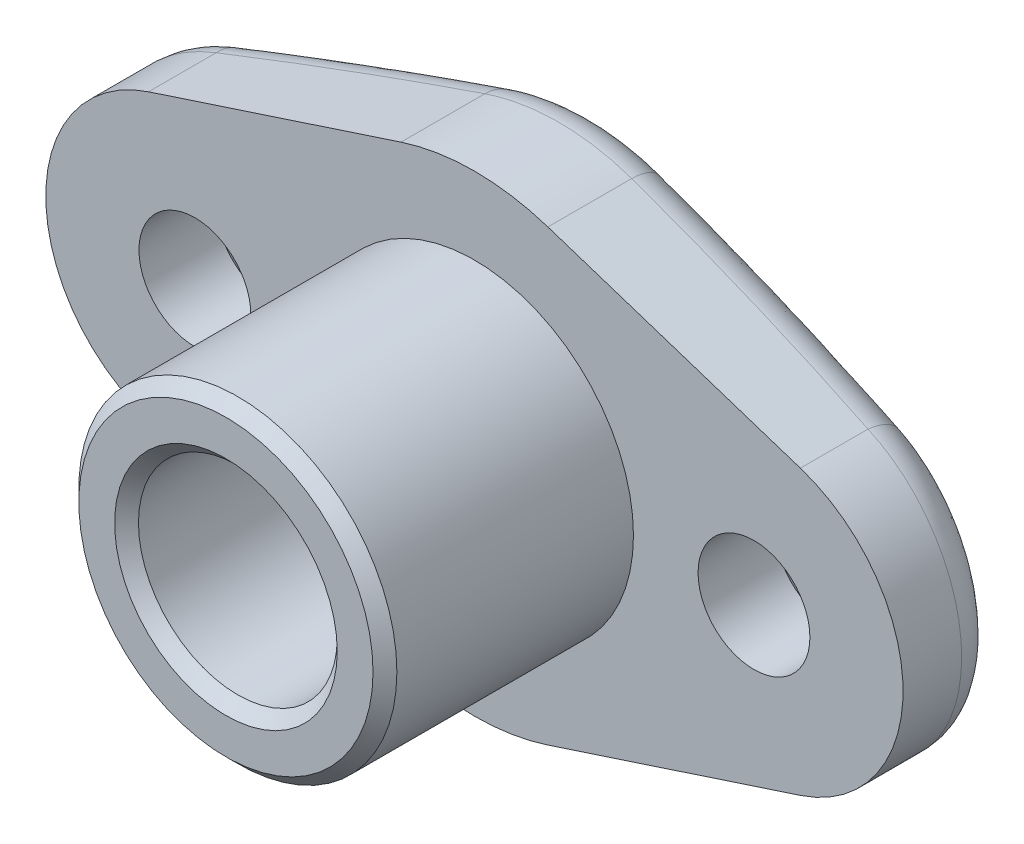
SolidWorks part; units mm, degrees
ref_plane "Front Plane" through (0, 0, 0) normal (0, 0, 1) x (1, 0, 0)
ref_plane "Top Plane" through (0, 0, 0) normal (0, 1, 0) x (1, 0, 0)
ref_plane "Right Plane" through (0, 0, 0) normal (1, 0, 0) x (0, 0, -1)
sketch "Sketch1" plane through (0, 0, 0) normal (0, 0, 1) x (1, 0, 0)
  line L0 (-10.4114, 4.5262) -> (-2.346, 7.1664)
  line L1 (2.346, 7.1664) -> (10.4114, 4.5262)
  line L2 (10.4114, -4.5262) -> (2.346, -7.1664)
  line L3 (-2.346, -7.1664) -> (-10.4114, -4.5262)
  line L4 (-8.9297, 0) -> (8.9297, 0) construction
  line L5 (-13.6922, 0) -> (13.6922, 0) construction
  circle A0 centre (0, 0) radius 7.5406
  circle A1 centre (8.9297, 0) radius 1.7859
  circle A2 centre (-8.9297, 0) radius 1.7859
  arc A3 (-10.4114, 4.5262) -> (-10.4114, -4.5262) centre (-8.9297, 0) ccw
  arc A4 (10.4114, -4.5262) -> (10.4114, 4.5262) centre (8.9297, 0) ccw
  circle A5 centre (0, 0) radius 3.175
  dimension "shaft dia" = 6.35
sketch "Sketch2" plane through (0, 0, 0) normal (0, 1, 0) x (1, 0, 0)
  line L0 (0, 0) -> (0, -11.9062) construction
  point P3 (0, -3.9688)
sketch "Sketch3" plane through (0, 0, 0) normal (0, 0, 1) x (1, 0, 0)
  line L0 (2.346, 7.1664) -> (10.4114, 4.5262) construction
  line L1 (10.4114, -4.5262) -> (2.346, -7.1664) construction
  line L2 (-10.4114, 4.5262) -> (-2.346, 7.1664) construction
  line L3 (-2.346, -7.1664) -> (-10.4114, -4.5262) construction
  line L4 (2.346, 7.1664) -> (10.4114, 4.5262)
  line L5 (10.4114, -4.5262) -> (2.346, -7.1664)
  line L6 (-10.4114, 4.5262) -> (-2.346, 7.1664)
  line L7 (-2.346, -7.1664) -> (-10.4114, -4.5262)
  arc A0 (10.4114, -4.5262) -> (10.4114, 4.5262) centre (8.9297, 0) ccw construction
  arc A1 (-10.4114, 4.5262) -> (-10.4114, -4.5262) centre (-8.9297, 0) ccw construction
  arc A2 (10.4114, -4.5262) -> (10.4114, 4.5262) centre (8.9297, 0) ccw
  arc A3 (-10.4114, 4.5262) -> (-10.4114, -4.5262) centre (-8.9297, 0) ccw
  arc A4 (-2.346, -7.1664) -> (2.346, -7.1664) centre (0, 0) ccw
  circle A5 centre (-8.9297, 0) radius 1.7859
  circle A6 centre (-8.9297, 0) radius 1.7859
  circle A7 centre (8.9297, 0) radius 1.7859
  circle A8 centre (8.9297, 0) radius 1.7859
  circle A9 centre (0, 0) radius 7.5406
  arc A10 (2.346, 7.1664) -> (-2.346, 7.1664) centre (0, 0) ccw
  circle A11 centre (0, 0) radius 3.175
  circle A12 centre (0, 0) radius 3.175 construction
  dimension "D1" = 0
  dimension "D2" = 0
  dimension "D3" = 0
  dimension "D4" = 0
extrude "Extrude1" add sketch "Sketch3" along normal up to vertex (3.9688 mm away) up to point (0, 0, 3.9688)
sketch "Sketch4" plane through (0, 0, 3.9688) normal (0, 0, 1) x (1, 0, 0)
  circle A0 centre (0, 0) radius 3.175 construction
  circle A1 centre (0, 0) radius 3.175
  circle A2 centre (0, 0) radius 5.08
  dimension "Sleeve O.D." = 10.16
extrude "Extrude2" add sketch "Sketch4" along normal up to vertex (7.9375 mm away) up to point (0, 0, 11.9062)
sketch "Sketch5" plane through (0, 0, 0) normal (0, 0, -1) x (-1, 0, 0)
  circle A0 centre (-8.9297, 0) radius 3.5719
  circle A1 centre (8.9297, 0) radius 3.5719
  dimension "D1" = 7.1437
extrude "Cut-Extrude1" cut sketch "Sketch5" against normal through all draft 50
sketch "Sketch6" plane through (0, 0, 0) normal (0, 1, 0) x (1, 0, 0)
  line L0 (13.6922, -0.9922) -> (13.6922, 0.508)
  line L1 (13.6922, 0.508) -> (-13.6922, 0.508)
  line L2 (-13.6922, 0.508) -> (-13.6922, -0.9922)
  line L3 (10.4114, 0) -> (13.6922, 0) construction
  arc A0 (-13.6922, -0.9922) -> (13.6922, -0.9922) centre (0, -94.9722) cw
  dimension "D1" = 0.508
  dimension "D2" = 0.9922
extrude "Cut-Extrude2" cut sketch "Sketch6" against normal mid plane 76.2
chamfer "Chamfer1" distance 0.381 angle 45 2 edges at (3.175, 0, 11.9062) (5.08, 0, 11.9062)
fillet "Fillet1" radius 1.27 8 edges at (-0.1513, 7.5391, 0.0001) (6.3844, 5.8444, 0.2148) (13.6692, 0.4673, 0.9888) (6.3844, -5.8444, 0.2148) (0.1513, -7.5391, 0.0001) (-6.3844, -5.8444, 0.2148) (-13.6692, -0.4673, 0.9888) (-6.3844, 5.8444, 0.2148)
ref_axis "Center Axis 1" through (-8.9297, 0, 3.9688) along (0, 0, -1)
ref_axis "Center Axis 2" through (8.9297, 0, 3.9688) along (0, 0, -1)
ref_axis "Center Axis 3" through (0, 0, 11.5253) along (0, 0, -1)
ref_plane "Contact Plane 1 " through (0, 0, 3.9688) normal (0, 0, 1) x (1, 0, 0)
sketch "Sketch8" plane through (0, 0, 0) normal (0, 0, 1) x (1, 0, 0)
  circle A0 centre (0, 0) radius 3.175
extrude "Cut-Extrude3" cut sketch "Sketch8" along normal through all
equation "\"D1@Sketch5\" = \"F@Sketch1\"*2"
equation "\"D2@Sketch6\" = \"G@Sketch2\"/4"
